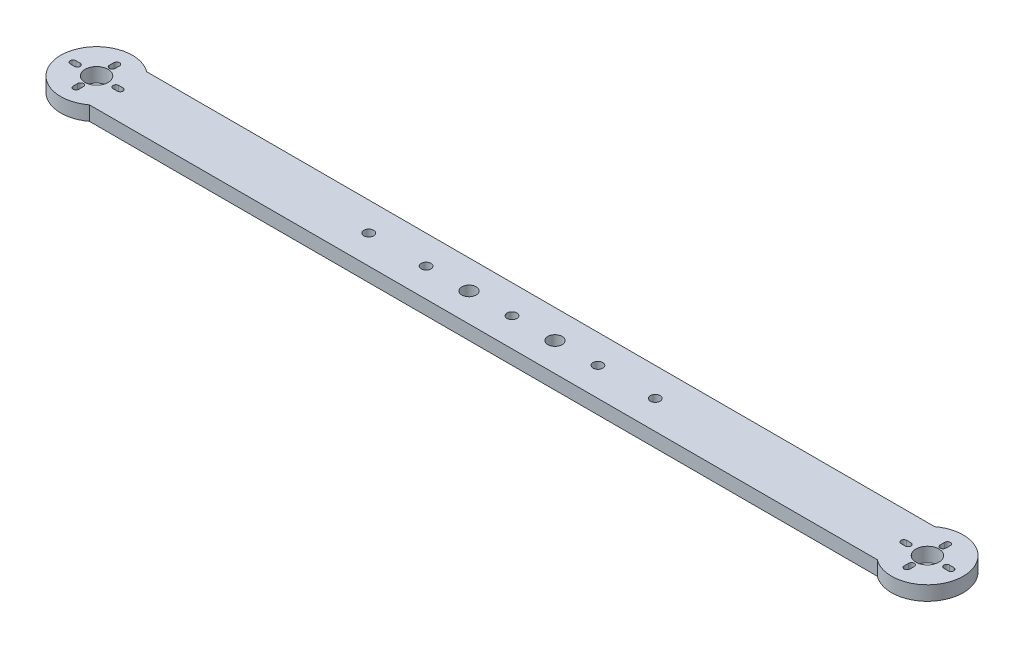
SolidWorks part; units mm, degrees
material "Thornel Mat VMA"
ref_plane "Front Plane" through (0, 0, 0) normal (0, 0, 1) x (1, 0, 0)
ref_plane "Top Plane" through (0, 0, 0) normal (0, 1, 0) x (1, 0, 0)
ref_plane "Right Plane" through (0, 0, 0) normal (1, 0, 0) x (0, 0, -1)
sketch "Sketch1" plane through (0, 0, 0) normal (0, 1, 0) x (1, 0, 0)
  line L0 (0, 12.7) -> (0, -12.7) construction
  line L1 (-174.625, 12.7) -> (174.625, 12.7)
  line L3 (-174.625, -12.7) -> (174.625, -12.7)
  arc A0 (-174.625, 12.7) -> (-174.625, -12.7) centre (-184.15, 0) ccw
  arc A1 (174.625, -12.7) -> (174.625, 12.7) centre (184.15, 0) ccw
  point P8 (0, 12.7)
  point P12 (0, 0)
  dimension "D3" = 31.75
  dimension "D4" = 31.75
extrude "Boss-Extrude1" add sketch "Sketch1" along normal blind 6.35
sketch "Sketch2" plane through (0, 6.35, 0) normal (0, 1, 0) x (1, 0, 0)
  line L0 (173.6914, 0) -> (175.6086, 0) construction
  line L1 (173.6914, 1.25) -> (175.6086, 1.25)
  line L2 (173.6914, -1.25) -> (175.6086, -1.25)
  line L3 (184.15, 0) -> (184.15, 3.2374) construction
  line L4 (194.6086, 0) -> (192.6914, 0) construction
  line L5 (194.6086, 1.25) -> (192.6914, 1.25)
  line L6 (194.6086, -1.25) -> (192.6914, -1.25)
  line L7 (184.15, 8.9209) -> (184.15, 6.921) construction
  line L8 (185.4, 8.9209) -> (185.4, 6.921)
  line L9 (182.9, 8.9209) -> (182.9, 6.921)
  line L10 (184.1914, -9.079) -> (184.1914, -7.079) construction
  line L11 (185.4414, -9.079) -> (185.4414, -7.079)
  line L12 (182.9414, -9.079) -> (182.9414, -7.079)
  line L13 (0, 0) -> (184.15, 0) construction
  line L14 (0, 0) -> (0, 12.7) construction
  line L15 (174.625, 12.7) -> (-174.625, 12.7) construction
  line L16 (-184.15, 0) -> (-184.15, 3.2374) construction
  line L17 (-184.1914, -9.079) -> (-184.1914, -7.079) construction
  line L18 (-185.4414, -9.079) -> (-185.4414, -7.079)
  line L19 (-182.9414, -9.079) -> (-182.9414, -7.079)
  line L20 (-184.15, 8.9209) -> (-184.15, 6.921) construction
  line L21 (-185.4, 8.9209) -> (-185.4, 6.921)
  line L22 (-182.9, 8.9209) -> (-182.9, 6.921)
  line L23 (-194.6086, 0) -> (-192.6914, 0) construction
  line L24 (-194.6086, 1.25) -> (-192.6914, 1.25)
  line L25 (-194.6086, -1.25) -> (-192.6914, -1.25)
  line L26 (-173.6914, 0) -> (-175.6086, 0) construction
  line L27 (-173.6914, 1.25) -> (-175.6086, 1.25)
  line L28 (-173.6914, -1.25) -> (-175.6086, -1.25)
  circle A0 centre (184.15, 0) radius 5.08
  arc A1 (173.6914, 1.25) -> (173.6914, -1.25) centre (173.6914, 0) ccw
  arc A2 (175.6086, -1.25) -> (175.6086, 1.25) centre (175.6086, 0) ccw
  arc A3 (194.6086, 1.25) -> (194.6086, -1.25) centre (194.6086, 0) cw
  arc A4 (192.6914, -1.25) -> (192.6914, 1.25) centre (192.6914, 0) cw
  arc A5 (185.4, 8.9209) -> (182.9, 8.9209) centre (184.15, 8.9209) ccw
  arc A6 (182.9, 6.921) -> (185.4, 6.921) centre (184.15, 6.921) ccw
  arc A7 (185.4414, -9.079) -> (182.9414, -9.079) centre (184.1914, -9.079) cw
  arc A8 (182.9414, -7.079) -> (185.4414, -7.079) centre (184.1914, -7.079) cw
  circle A9 centre (-184.15, 0) radius 5.08
  arc A10 (-185.4414, -9.079) -> (-182.9414, -9.079) centre (-184.1914, -9.079) ccw
  arc A11 (-182.9414, -7.079) -> (-185.4414, -7.079) centre (-184.1914, -7.079) ccw
  arc A12 (-185.4, 8.9209) -> (-182.9, 8.9209) centre (-184.15, 8.9209) cw
  arc A13 (-182.9, 6.921) -> (-185.4, 6.921) centre (-184.15, 6.921) cw
  arc A14 (-194.6086, 1.25) -> (-194.6086, -1.25) centre (-194.6086, 0) ccw
  arc A15 (-192.6914, -1.25) -> (-192.6914, 1.25) centre (-192.6914, 0) ccw
  arc A16 (-173.6914, 1.25) -> (-173.6914, -1.25) centre (-173.6914, 0) cw
  arc A17 (-175.6086, -1.25) -> (-175.6086, 1.25) centre (-175.6086, 0) cw
  point P4 (174.65, 0)
  point P12 (193.65, 0)
  point P19 (184.15, 7.921)
  point P26 (184.1914, -8.079)
  point P41 (-184.1914, -8.079)
  point P48 (-184.15, 7.921)
  point P55 (-193.65, 0)
  point P62 (-174.65, 0)
  dimension "D4" = 10.16
  dimension "D1" = 16
  dimension "D2" = 19
  dimension "D3" = 184.15
  dimension "D5" = 1.9999
extrude "Cut-Extrude1" cut sketch "Sketch2" against normal through all
sketch "Sketch3" plane through (0, 6.35, 0) normal (0, 1, 0) x (1, 0, 0)
  circle A0 centre (0, 0) radius 2.159
  circle A1 centre (38.1, 0) radius 2.159
  circle A2 centre (-38.1, 0) radius 2.159
  dimension "D1" = 38.1
  dimension "D3" = 4.318
  dimension "D4" = 4.318
  dimension "D5" = 4.318
  dimension "D2" = 38.1
extrude "Cut-Extrude2" cut sketch "Sketch3" against normal through all
sketch "Sketch4" plane through (0, 6.35, 0) normal (0, 1, 0) x (1, 0, 0)
  circle A0 centre (-19.05, 0) radius 3.175
  circle A1 centre (19.05, 0) radius 3.175
  dimension "D1" = 19.05
  dimension "D2" = 19.05
extrude "Cut-Extrude3" cut sketch "Sketch4" against normal through all
sketch "Sketch5" plane through (0, 6.35, 0) normal (0, 1, 0) x (1, 0, 0)
  line L0 (0, 12.7) -> (0, -22.99) construction
  line L1 (174.625, 12.7) -> (-174.625, 12.7) construction
  circle A0 centre (63.5, 0) radius 2.159
  circle A1 centre (184.15, 0) radius 5.08 construction
  circle A2 centre (-63.5, 0) radius 2.159
  dimension "D1" = 4.318
  dimension "D2" = 120.65
extrude "Cut-Extrude4" cut sketch "Sketch5" against normal through all
